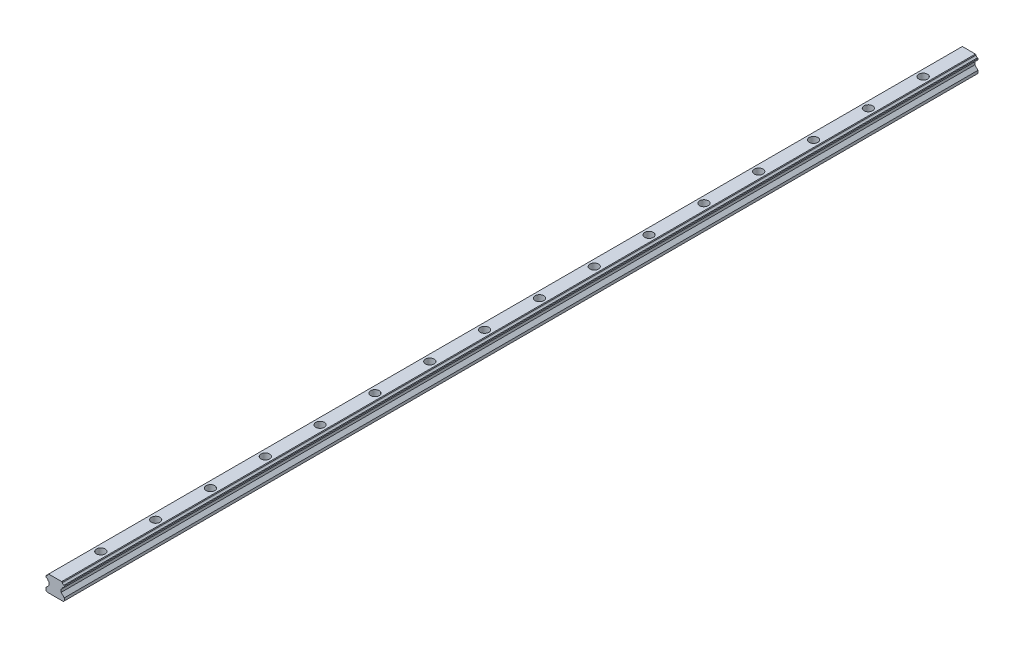
SolidWorks part; units mm, degrees
material "Plain Carbon Steel"
ref_plane "Front Plane" through (0, 0, 0) normal (0, 0, 1) x (1, 0, 0)
ref_plane "Top Plane" through (0, 0, 0) normal (0, 1, 0) x (1, 0, 0)
ref_plane "Right Plane" through (0, 0, 0) normal (1, 0, 0) x (0, 0, -1)
sketch "Sketch1" plane through (0, 0, 0) normal (0, 0, 1) x (1, 0, 0)
  line L0 (0, 13.3681) -> (0, -3.2505) construction
  line L1 (-6.55, -4.115) -> (-6.55, -7.045)
  line L2 (-6.55, -5.58) -> (0, -5.58) construction
  line L3 (-6.55, -7.045) -> (-10, -10.495)
  line L4 (-10, -10.495) -> (-10, -13.495)
  line L5 (-10, -13.495) -> (-9, -14.495)
  line L6 (-9, -14.495) -> (0, -14.495)
  line L7 (-6.55, -4.115) -> (-7.7681, -2.8969)
  line L8 (-10, -0.665) -> (-10, 0.665)
  line L9 (-10, 0.665) -> (-9.4697, 1.1953)
  line L10 (-7.16, 3.505) -> (0, 3.505)
  line L11 (-10, -0.665) -> (-10, -10.495) construction
  line L12 (-10, 0) -> (0, 0) construction
  line L13 (-7.7681, 2.8969) -> (-7.16, 3.505)
  line L14 (-9.4697, -1.1953) -> (-10, -0.665)
  line L15 (0, 3.505) -> (0, -14.495)
  arc A0 (-9.4697, 1.1953) -> (-7.7681, 2.8969) centre (-9.7486, 3.1758) ccw
  arc A1 (-9.4697, -1.1953) -> (-7.7681, -2.8969) centre (-9.7486, -3.1758) cw
  dimension "D10" = 4
  dimension "D1" = 2.93
  dimension "D2" = 6.55
  dimension "D3" = 9
  dimension "D4" = 7.16
  dimension "D5" = 3
  dimension "D6" = 1.33
  dimension "D7" = 18
  dimension "D8" = 45
  dimension "D9" = 45
  dimension "D11" = 0.75
  dimension "D12" = 0.86
extrude "Boss-Extrude1" add sketch "Sketch1" along normal blind 500
mirror "Mirror1" about plane through (0, 3.505, 500) normal (-1, 0, 0) of "Boss-Extrude1"
sketch "Sketch2" plane through (0, 3.505, 0) normal (0, 1, 0) x (1, 0, 0)
  line L0 (0, 130.187) -> (0, 31.9327) construction
  line L1 (7.16, 0) -> (-7.16, 0) construction
  circle A0 centre (0, -30) radius 3
  dimension "D1" = 6
  dimension "D2" = 30
extrude "Cut-Extrude1" cut sketch "Sketch2" against normal through all
sketch "Sketch3" plane through (0, 3.505, 0) normal (0, 1, 0) x (1, 0, 0)
  circle A0 centre (0, -30) radius 4.75
  dimension "D1" = 9.5
extrude "Cut-Extrude2" cut sketch "Sketch3" against normal blind 8.5
pattern_linear "LPattern1" count 100 spacing 60 along (0, 0, 1) of "Cut-Extrude1", "Cut-Extrude2"
mirror "Mirror2" about plane through (-9.7486, -3.1758, 0) normal (0, 0, -1) of bodies 106
equation "\"length\"= 1000mm"
equation "\"D1@Boss-Extrude1\" = ( \"work_area_width\" - 100 ) / 2"
equation "\"M5_tap\"=4.2mm"
equation "\"M5_clearence\"=5.5mm"
equation "\"M6_tap\"=5mm"
equation "\"M6_clearence\"=6.6mm"
equation "\"work_area_width\"=1100mm"
equation "\"work_area_depth\"=900mm"
